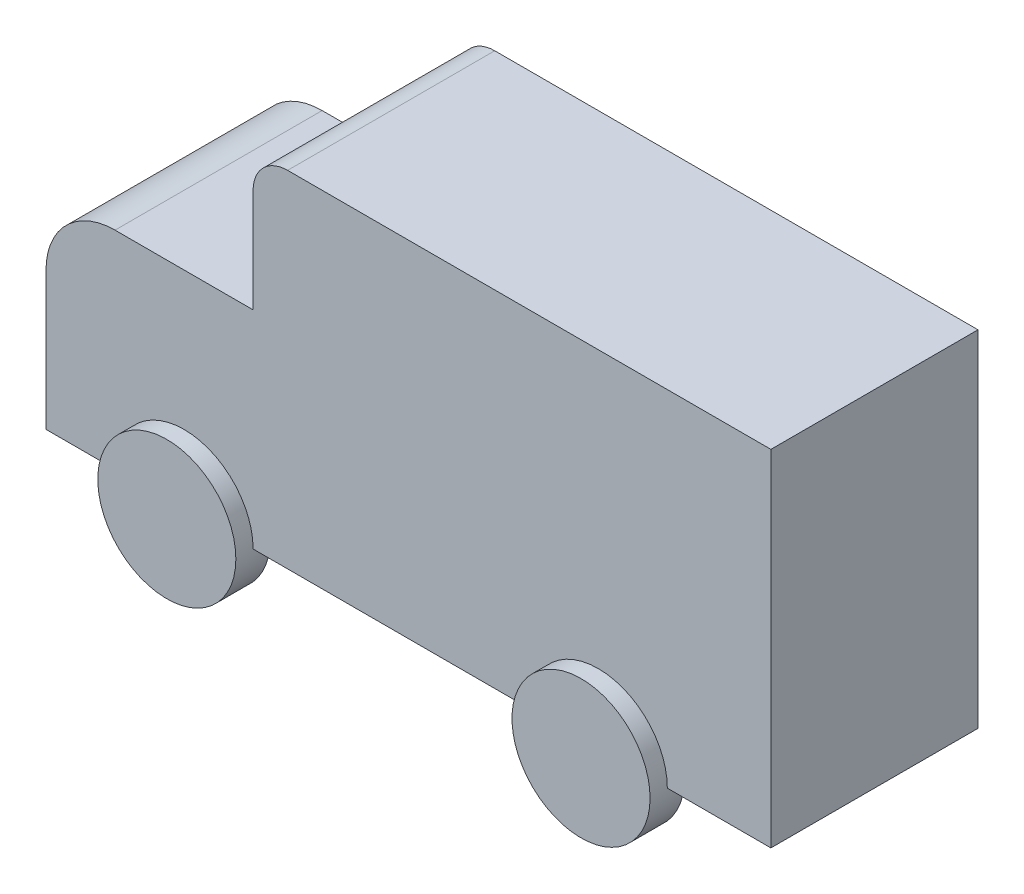
SolidWorks part; units mm, degrees
ref_plane "정면" through (0, 0, 0) normal (0, 0, 1) x (1, 0, 0)
ref_plane "윗면" through (0, 0, 0) normal (0, 1, 0) x (1, 0, 0)
ref_plane "우측면" through (0, 0, 0) normal (1, 0, 0) x (0, 0, -1)
sketch "스케치1" plane through (0, 0, 0) normal (0, 0, 1) x (1, 0, 0)
  line L1 (-1500, -1000) -> (1500, -1000)
  line L2 (-1500, 200) -> (-1500, 800)
  line L3 (-1300, 1000) -> (1500, 1000)
  line L4 (1500, -1000) -> (1500, 1000)
  line L5 (-1500, -1000) -> (1500, 1000) construction
  line L6 (-1500, 1000) -> (1500, -1000) construction
  line L7 (-2300, 200) -> (-1500, 200)
  line L8 (-2700, -200) -> (-2700, -1000)
  line L9 (-2700, -1000) -> (-1500, -1000)
  line L10 (-1500, 200) -> (-1500, -1000)
  circle A0 centre (-1900, -1000) radius 400
  circle A1 centre (500, -1000) radius 400
  arc A2 (-2700, -200) -> (-2300, 200) centre (-2300, -200) cw
  arc A3 (-1500, 800) -> (-1300, 1000) centre (-1300, 800) cw
  point P0 (0, 0)
  point P15 (-2700, 200)
  dimension "D5" = 800
  dimension "D6" = 800
  dimension "D7" = 2400
  dimension "D9" = 400
  dimension "D10" = 200
  dimension "D1" = 3000
  dimension "D2" = 2000
  dimension "D3" = 1200
  dimension "D4" = 1200
  dimension "D8" = 0
extrude "보스-돌출1" add sketch "스케치1" against normal mid plane 1200 contours A2 L8 L9 A0 L10 L7 | A3 L2 L10 L1 A1 L4 L3 | L9 A0 | L1 A1 region at (-19.7159, 34.9228, 0) region at (500, -830.2347, 0) region at (-2128.3553, -321.5169, 0) region at (-1900, -830.2347, 0)
extrude "보스-돌출2" add sketch "스케치1<3>" along normal mid plane 200 from offset 600 contours L9 A0 | L9 A0 | L1 A1 | L1 A1 region at (500, -1169.7653, 0) region at (500, -830.2347, 0) region at (-1900, -1169.7653, 0) region at (-1900, -830.2347, 0)
sketch "스케치1<3>" plane through (0, 0, 0) normal (0, 0, 1) x (1, 0, 0) same geometry as "스케치1"
mirror "대칭 복사1" about plane through (0, 0, 0) normal (0, 0, 1) of "보스-돌출2"
